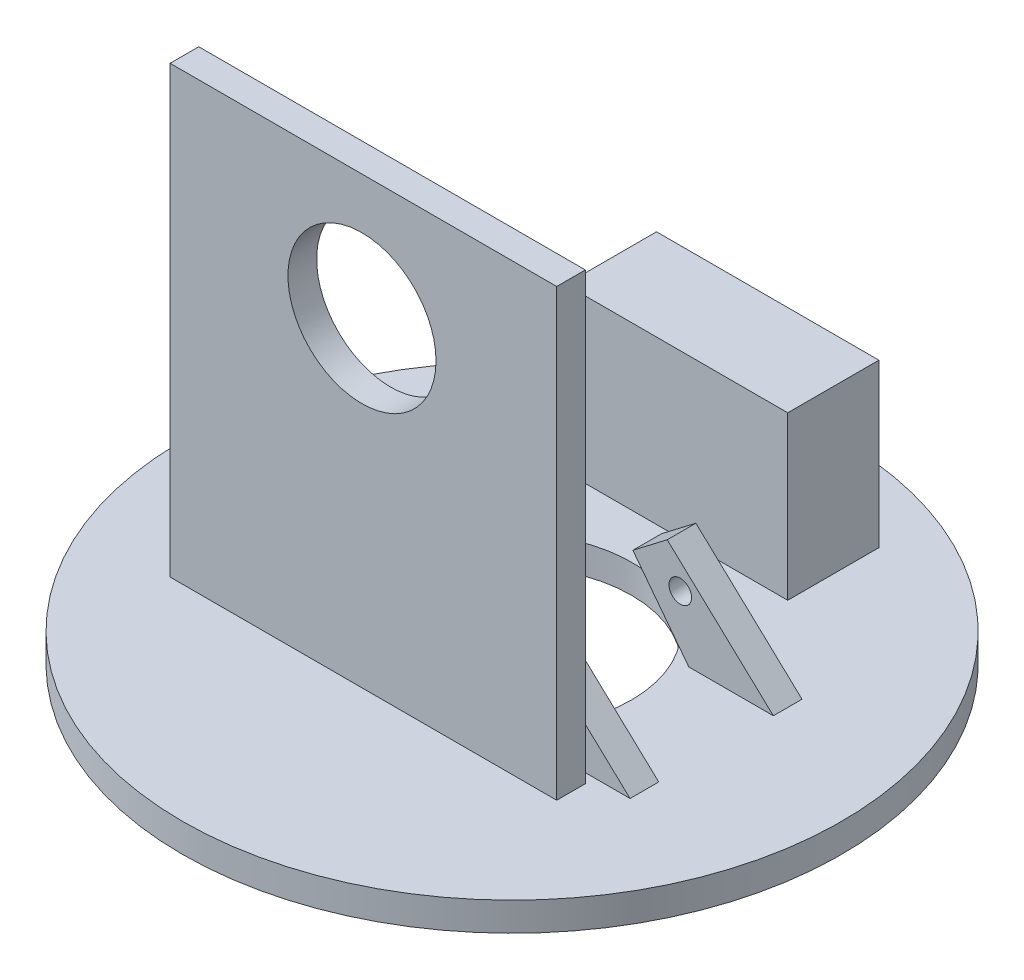
SolidWorks part; units mm, degrees
ref_plane "前视基准面" through (0, 0, 0) normal (0, 0, 1) x (1, 0, 0)
ref_plane "上视基准面" through (0, 0, 0) normal (0, 1, 0) x (1, 0, 0)
ref_plane "右视基准面" through (0, 0, 0) normal (1, 0, 0) x (0, 0, -1)
sketch "草图1" plane through (0, 0, 0) normal (0, 1, 0) x (1, 0, 0)
  circle A0 centre (0, 0) radius 34.5
  dimension "D1" = 69
extrude "凸台-拉伸1" add sketch "草图1" along normal blind 3
sketch "草图2" plane through (0, 3, 0) normal (0, 1, 0) x (1, 0, 0)
  circle A0 centre (0, 0) radius 12.5
  dimension "D1" = 25
extrude "切除-拉伸1" cut sketch "草图2" against normal blind 3
sketch "草图3" plane through (0, 0, 0) normal (0, 0, 1) x (1, 0, 0)
  line L0 (-12.5, 3) -> (-6.6458, 10.6493)
  line L1 (34.5, 3) -> (-34.5, 3) construction
  line L2 (-6.6458, 10.6493) -> (-10.2403, 13.4003)
  line L3 (-10.2403, 13.4003) -> (-21.3528, 3)
  line L4 (-21.3528, 3) -> (-12.5, 3)
  circle A0 centre (-11.6067, 9.4208) radius 1.183
extrude "凸台-拉伸2" add sketch "草图3" along normal blind 3 from offset 6
extrude "凸台-拉伸3" add sketch "草图3<2>" against normal blind 3 from offset 6 offset against normal yes
sketch "草图3<2>" plane through (0, 0, 0) normal (0, 0, 1) x (1, 0, 0) same geometry as "草图3"
mirror "镜向1" about plane through (0, 0, 0) normal (1, 0, 0) of "凸台-拉伸2", "凸台-拉伸3"
sketch "草图4" plane through (0, 0, 0) normal (0, 0, 1) x (1, 0, 0)
  line L0 (-22.7952, 3) -> (-22.7952, 49.5775)
  line L1 (34.5, 3) -> (-34.5, 3) construction
  line L2 (-22.7952, 49.5775) -> (17.6713, 49.5775)
  line L3 (17.6713, 49.5775) -> (17.6713, 3)
  line L4 (17.6713, 3) -> (-22.7952, 3)
extrude "凸台-拉伸6" add sketch "草图4" along normal blind 3 from offset 10
sketch "草图5" plane through (0, 0, 13) normal (0, 0, 1) x (1, 0, 0)
  circle A0 centre (-2.7109, 36.5087) radius 7.75
  dimension "D1" = 15.5
extrude "切除-拉伸2" cut sketch "草图5" against normal blind 3
sketch "草图6" plane through (0, 3, 0) normal (0, 1, 0) x (1, 0, 0)
  line L0 (0, 0) -> (0, 44.1845) construction
  line L1 (-11.6375, 26.7594) -> (11.6375, 26.7594)
  line L2 (-11.6375, 26.7594) -> (-11.6375, 17.2194)
  line L3 (-11.6375, 17.2194) -> (11.6375, 17.2194)
  line L4 (11.6375, 26.7594) -> (11.6375, 17.2194)
extrude "凸台-拉伸7" add sketch "草图6" along normal blind 17
